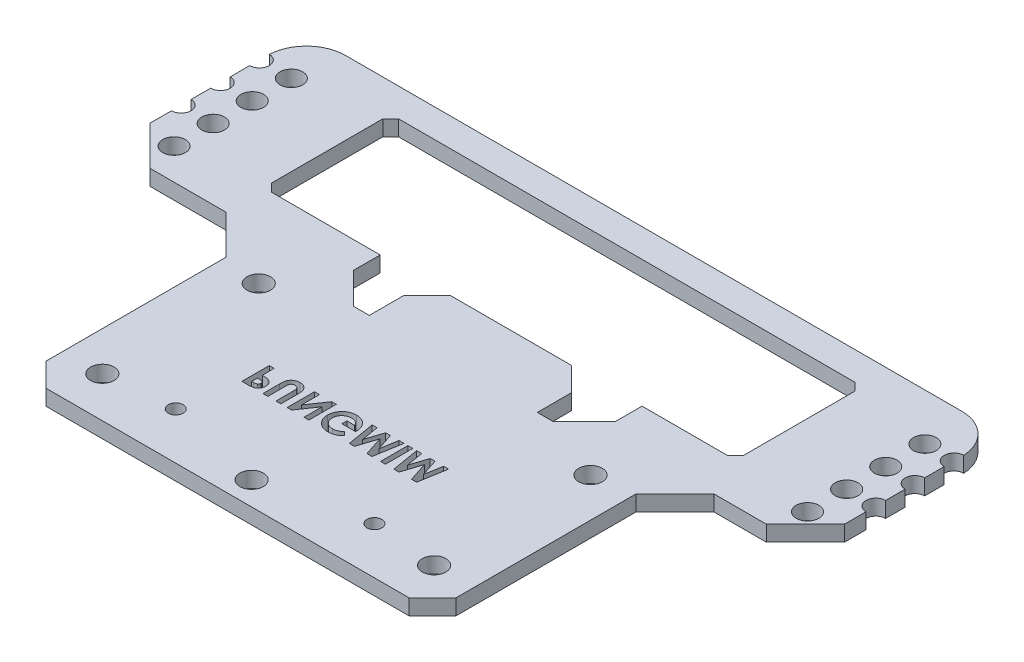
SolidWorks part; units mm, degrees
ref_plane "Front Plane" through (0, 0, 0) normal (0, 0, 1) x (1, 0, 0)
ref_plane "Top Plane" through (0, 0, 0) normal (0, 1, 0) x (1, 0, 0)
ref_plane "Right Plane" through (0, 0, 0) normal (1, 0, 0) x (0, 0, -1)
sketch "Sketch2" plane through (0, 0, 0) normal (0, 1, 0) x (1, 0, 0)
  line L1 (-35, 25) -> (35, 25)
  line L2 (-35, 25) -> (-35, -25)
  line L3 (-35, -25) -> (35, -25)
  line L4 (35, 25) -> (35, -25)
  line L5 (-35, 25) -> (35, -25) construction
  line L6 (-35, -25) -> (35, 25) construction
  point P0 (0, 0)
  dimension "D1" = 50
  dimension "D2" = 70
extrude "Boss-Extrude1" add sketch "Sketch2" along normal blind 2
sketch "Sketch3" plane through (0, 2, 0) normal (0, 1, 0) x (1, 0, 0)
  line L0 (-35, -25) -> (35, -25) construction
  line L1 (-35, 25) -> (-22, 25)
  line L2 (-35, 25) -> (-35, -25)
  line L3 (-35, -25) -> (-22, -25)
  line L4 (-22, 25) -> (-22, -25)
  line L6 (35, 25) -> (22, 25)
  line L7 (35, 25) -> (35, -25)
  line L8 (35, -25) -> (22, -25)
  line L9 (22, 25) -> (22, -25)
extrude "Cut-Extrude1" cut sketch "Sketch3" against normal through all
ref_plane "Plane1" through (22, 2, 25) normal (1, 0, 0) x (0, 0, -1)
sketch "Sketch9" plane through (0, 2, 0) normal (0, 1, 0) x (1, 0, 0)
  line L0 (-22, -25) -> (-22, 25) construction
  line L1 (-22, 25) -> (22, 25)
  line L2 (-22, 25) -> (-22, 31)
  line L3 (-22, 31) -> (22, 31)
  line L4 (22, 25) -> (22, 31)
  line L5 (-22, 10.4486) -> (-33, 10.4486)
  line L6 (-22, 10.4486) -> (-22, 31)
  line L7 (-22, 31) -> (-33, 31)
  line L8 (-33, 10.4486) -> (-33, 31)
  line L10 (22, 31) -> (33, 31)
  line L11 (22, 31) -> (22, 10.4486)
  line L12 (22, 10.4486) -> (33, 10.4486)
  line L13 (33, 31) -> (33, 10.4486)
  dimension "D1" = 6
  dimension "D2" = 11
  dimension "D3" = 11
extrude "Extrude-Thin1" add sketch "Sketch9" against normal blind 2 thin contours L3 thin type one direction wall 10
sketch "Sketch13" plane through (0, 2, 0) normal (0, 1, 0) x (1, 0, 0)
sketch "Sketch14" plane through (0, 2, 0) normal (0, 1, 0) x (1, 0, 0)
sketch "Sketch15" plane through (0, 2, 0) normal (0, 1, 0) x (1, 0, 0)
  line L1 (-30, 26.4189) -> (30, 26.4189)
  line L2 (-30, 26.4189) -> (-30, 11.4189)
  line L3 (-30, 11.4189) -> (30, 11.4189)
  line L4 (30, 26.4189) -> (30, 11.4189)
  dimension "D1" = 60
extrude "Cut-Extrude2" cut sketch "Sketch15" against normal through all
chamfer "Chamfer1" distance 1 angle 45 rebuild error yes
sketch "Sketch17" plane through (0, 2, 0) normal (0, 1, 0) x (1, 0, 0)
sketch "Sketch20" plane through (0, 2, 0) normal (0, 1, 0) x (1, 0, 0)
  line L1 (-22, 31) -> (-44.4, 31)
  line L2 (-22, 31) -> (-22, 6)
  line L3 (-22, 6) -> (-44.4, 6)
  line L4 (-44.4, 31) -> (-44.4, 6)
  line L5 (22, 31) -> (44.4, 31)
  line L6 (22, 31) -> (22, 6)
  line L7 (22, 6) -> (44.4, 6)
  line L8 (44.4, 31) -> (44.4, 6)
  dimension "D1" = 25
  dimension "D2" = 25
  dimension "D3" = 22.4
  dimension "D4" = 22.4
extrude "Boss-Extrude5" add sketch "Sketch20" against normal through all
sketch "Sketch21" plane through (0, 2, 0) normal (0, 1, 0) x (1, 0, 0)
  line L1 (-30, 27.3746) -> (30.3345, 27.3746)
  line L2 (-30, 27.3746) -> (-30, 11.1231)
  line L3 (-30, 11.1231) -> (30.3345, 11.1231)
  line L4 (30.3345, 27.3746) -> (30.3345, 11.1231)
extrude "Cut-Extrude3" cut sketch "Sketch21" against normal through all
chamfer "Chamfer5" distance 1 angle 45 4 edges at (-30, 1, -27.3746) (-30, 1, -11.1231) (30.3345, 1, -11.1231) (30.3345, 1, -27.3746)
sketch "Sketch22" plane through (0, 2, 0) normal (0, 1, 0) x (1, 0, 0)
  line L1 (-22, 6) -> (-24.7, 6)
  line L2 (-22, 6) -> (-22, -25)
  line L3 (-22, -25) -> (-24.7, -25)
  line L4 (-24.7, 6) -> (-24.7, -25)
  line L5 (22, 6) -> (27.7219, 6)
  line L6 (22, 6) -> (22, -25)
  line L7 (22, -25) -> (27.7219, -25)
  line L8 (27.7219, 6) -> (27.7219, -25)
extrude "Boss-Extrude6" add sketch "Sketch22" against normal through all
chamfer "Chamfer6" distance 5 angle 45 4 edges at (-24.7, 1, -6) (-44.4, 1, -6) (27.7219, 1, -6) (44.4, 1, -6)
fillet "Fillet2" radius 5 2 edges at (-44.4, 1, -31) (44.4, 1, -31)
chamfer "Chamfer8" distance 3 angle 45 2 edges at (27.7219, 1, 25) (-24.7, 1, 25)
sketch "Sketch23" plane through (0, 2, 0) normal (0, 1, 0) x (1, 0, 0)
  line L0 (-29, 11.1231) -> (29.3345, 11.1231) construction
  line L1 (-9.0956, 3.7335) -> (-15.0956, 3.7335)
  line L2 (-9.0956, 3.7335) -> (-9.0956, 11.1231)
  line L3 (-9.0956, 11.1231) -> (-15.0956, 11.1231)
  line L4 (-15.0956, 3.7335) -> (-15.0956, 11.1231)
  line L6 (12.3886, 3.7335) -> (18.3886, 3.7335)
  line L7 (12.3886, 3.7335) -> (12.3886, 11.1231)
  line L8 (12.3886, 11.1231) -> (18.3886, 11.1231)
  line L9 (18.3886, 3.7335) -> (18.3886, 11.1231)
  dimension "D1" = 6
  dimension "D2" = 6
extrude "Cut-Extrude4" cut sketch "Sketch23" against normal through all
sketch "Sketch24" plane through (0, 2, 0) normal (0, 1, 0) x (1, 0, 0)
  line L0 (-11.6114, -22) -> (14.7886, -22) construction
  circle A0 centre (1.5886, -22) radius 1.5
  dimension "D1" = 3
extrude "Cut-Extrude5" cut sketch "Sketch24" against normal through all
chamfer "Chamfer11" distance 3 angle 45 2 edges at (-9.0956, 1, -11.1231) (12.3886, 1, -11.1231)
ref_plane "Plane2" through (18.3886, 0, -3.7335) normal (0, 1, 0) x (1, 0, 0)
chamfer "Chamfer12" distance 4 angle 45 2 edges at (-15.0956, 1, -3.7335) (18.3886, 1, -3.7335)
sketch "Sketch26" plane through (0, 2, 0) normal (0, 1, 0) x (1, 0, 0)
  circle A0 centre (-11.1114, -19) radius 0.95
  circle A1 centre (14.2886, -19) radius 0.95
extrude "Cut-Extrude7" cut sketch "Sketch26" against normal through all
sketch "Sketch27" plane through (0, 2, 0) normal (0, 1, 0) x (1, 0, 0)
  circle A0 centre (-19.7, 0.2) radius 1.5
  circle A1 centre (-19.7, -19.8) radius 1.5
  circle A2 centre (22.7219, 0.2) radius 1.5
  circle A3 centre (22.7219, -19.8) radius 1.5
extrude "Cut-Extrude8" cut sketch "Sketch27" against normal through all
sketch "Sketch28" plane through (0, 0, 0) normal (0, -1, 0) x (1, 0, 0)
  text T0 "<b>PUNGMIM</b>"
extrude "Cut-Extrude10" cut sketch "Sketch28" against normal blind 2
sketch "Sketch29" plane through (0, 2, 0) normal (0, 1, 0) x (1, 0, 0)
sketch "Sketch30" plane through (0, 2, 0) normal (0, 1, 0) x (1, 0, 0)
  circle A0 centre (-40.33, 25) radius 1.45
  circle A1 centre (-40.33, 20) radius 1.45
  circle A2 centre (-40.33, 15) radius 1.45
  circle A3 centre (-40.33, 10) radius 1.45
  circle A4 centre (40.67, 25) radius 1.45
  circle A5 centre (40.67, 20) radius 1.45
  circle A6 centre (40.67, 15) radius 1.45
  circle A7 centre (40.67, 10) radius 1.45
extrude "Cut-Extrude11" cut sketch "Sketch30" against normal through all
sketch "Sketch32" plane through (0, 2, 0) normal (0, 1, 0) x (1, 0, 0)
  line L0 (-44.4, 26) -> (-44.4, 11) construction
  line L1 (44.4, 11) -> (44.4, 26) construction
  circle A0 centre (-44.4, 25) radius 1.25
  circle A1 centre (-44.4, 20) radius 1.25
  circle A2 centre (-44.4, 15) radius 1.25
  circle A3 centre (44.4, 25) radius 1.25
  circle A4 centre (44.4, 20) radius 1.25
  circle A5 centre (44.4, 15) radius 1.25
  dimension "D1" = 2.5
  dimension "D2" = 2.5
  dimension "D3" = 2.5
  dimension "D4" = 2.5
  dimension "D5" = 2.5
  dimension "D6" = 2.5
extrude "Cut-Extrude12" cut sketch "Sketch32" against normal through all
ref_plane "Plane3" through (-11.0956, 0, -3.7335) normal (0.7071, 0, 0.7071) x (0.7071, 0, -0.7071)
